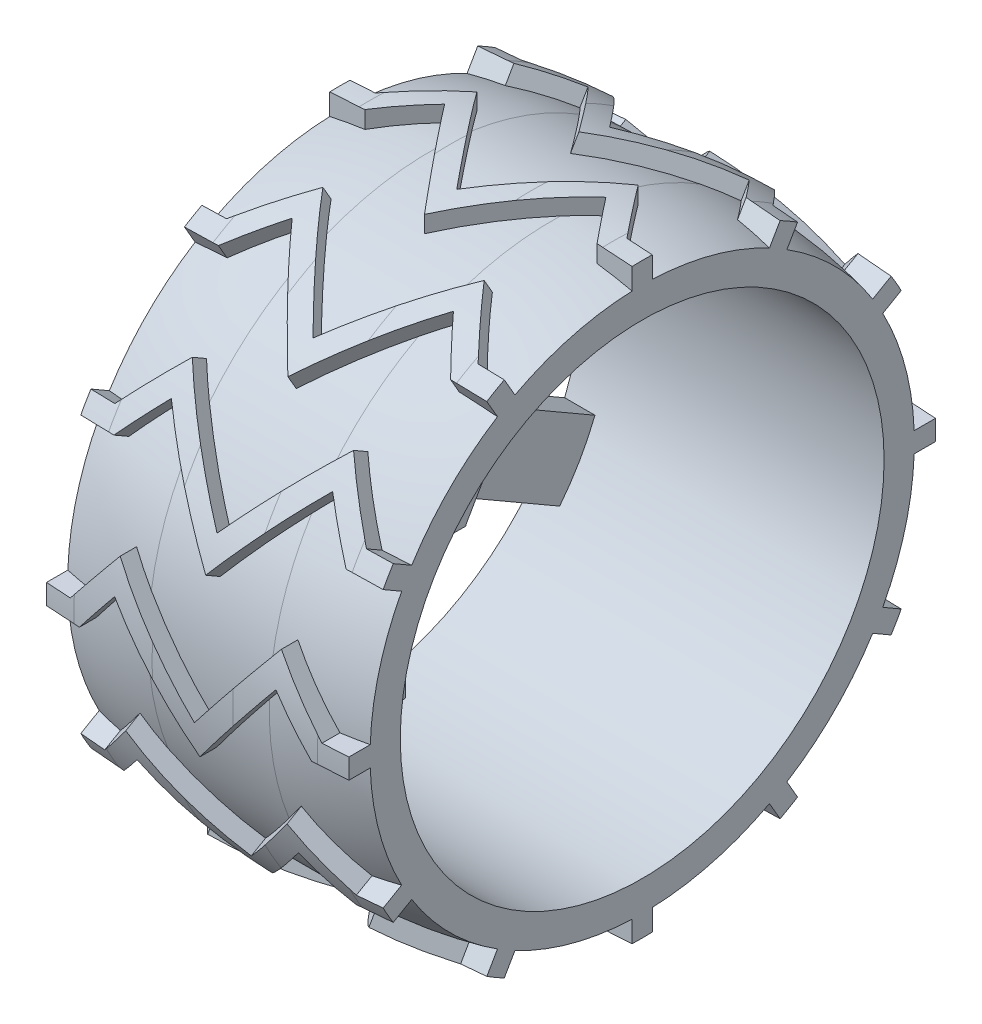
SolidWorks part; units mm, degrees
material "ABS"
ref_plane "Přední rovina" through (0, 0, 0) normal (0, 0, 1) x (1, 0, 0)
ref_plane "Horní rovina" through (0, 0, 0) normal (0, 1, 0) x (1, 0, 0)
ref_plane "Pravá rovina" through (0, 0, 0) normal (1, 0, 0) x (0, 0, -1)
sketch "Skica1" plane through (0, 0, 0) normal (0, 0, 1) x (1, 0, 0)
  line L0 (0, 0) -> (-19.9482, 0) construction
  line L1 (0, 0) -> (0, 24) construction
  line L2 (15, 24) -> (-15, 24)
  line L3 (-15, 24) -> (-15, 27)
  line L4 (0, 24) -> (0, 28) construction
  line L5 (6, 28) -> (-6, 28)
  line L6 (15, 24) -> (15, 27)
  arc A0 (-15, 27) -> (-6, 28) centre (-6, -13) cw
  arc A1 (15, 27) -> (6, 28) centre (6, -13) ccw
  dimension "D1" = 56
  dimension "D2" = 15
  dimension "D3" = 3
  dimension "D4" = 4
  dimension "D5" = 6
revolve "Rotovat1" add sketch "Skica1" angle 360 about L0 other way angle 360
ref_plane "Rovina1" through (0, 30, 0) normal (0, 1, 0) x (1, 0, 0)
sketch "Skica3" plane through (0, 30, 0) normal (0, 1, 0) x (1, 0, 0)
  line L0 (-15, 0) -> (-12, 0)
  line L1 (-15, 27) -> (-15, -27) construction
  line L2 (-12, 0) -> (-8, 5)
  line L3 (-8, 5) -> (-4, 0)
  line L4 (0, 0) -> (-10.2838, 0) construction
  line L5 (0, 0) -> (0, -5) construction
  line L6 (-8, 5) -> (-8, 0) construction
  line L7 (-4, 0) -> (0, -5)
  line L8 (4, 0) -> (0, -5)
  line L9 (8, 5) -> (4, 0)
  line L10 (12, 0) -> (8, 5)
  line L11 (15, 0) -> (12, 0)
  dimension "D1" = 5
  dimension "D2" = 3
extrude "Vysunout tenkostěnný1" add sketch "Skica3" against normal blind 10 thin thin type mid plane wall 2
pattern_circular "Kruhové pole1" count 12 over 360 about axis through (0, 0, 0) along (1, 0, 0) of "Vysunout tenkostěnný1"
sketch "Skica4" plane through (0, 0, 0) normal (1, 0, 0) x (0, 0, -1)
  circle A0 centre (0, 0) radius 24
  circle A1 centre (0, 0) radius 27
  circle A2 centre (0, 0) radius 24 construction
  dimension "D1" = 3
extrude "Odebrat vysunutím2" cut sketch "Skica4" against normal mid plane 30 contours A0 region at (0, 0, 0)
sketch "Skica5" plane through (0, 0, 0) normal (1, 0, 0) x (0, 0, -1)
  circle A0 centre (0, 0) radius 30
  circle A1 centre (0, 0) radius 24 construction
  circle A2 centre (0, 0) radius 40
  dimension "D1" = 6
  dimension "D2" = 10
extrude "Odebrat vysunutím3" cut sketch "Skica5" against normal mid plane 30
sketch "Skica6" plane through (0, 0, 0) normal (0, 0, 1) x (1, 0, 0)
  line L0 (-15, 26.9815) -> (-15, 29.9833) construction
  line L1 (-2, 28.618) -> (-4, 28.618) construction
  line L2 (-2, 28.618) -> (4, 28.618) construction
  line L3 (-2, 29.618) -> (4, 29.618)
  line L4 (-2, 29.618) -> (-4, 29.618)
  line L5 (-15, 29.113) -> (-18.0891, 33.8325)
  line L6 (-18.0891, 33.8325) -> (1.0133, 32.6178)
  line L7 (1.0133, 32.6178) -> (17.1086, 33.5822)
  line L8 (17.1086, 33.5822) -> (15, 29.113)
  line L9 (0, 0) -> (-14.4667, 0) construction
  line L10 (15, 26.9815) -> (15, 29.9833) construction
  arc A4 (-12, 28.2983) -> (-14, 28.118) centre (-4, -71.632) ccw construction
  arc A5 (-4, 28.618) -> (-12, 28.2983) centre (-4, -71.632) ccw construction
  arc A6 (14, 28.118) -> (12, 28.2983) centre (4, -71.632) ccw construction
  arc A7 (12, 28.2983) -> (4, 28.618) centre (4, -71.632) ccw construction
  arc A8 (15, 29.113) -> (12.0798, 29.2951) centre (7.2394, -71.8391) ccw
  arc A9 (12.0798, 29.2951) -> (4, 29.618) centre (4, -71.632) ccw
  arc A10 (-4, 29.618) -> (-12.0798, 29.2951) centre (-4, -71.632) ccw
  arc A11 (-12.0798, 29.2951) -> (-15, 29.113) centre (-7.2394, -71.8391) ccw
revolve "Odebrat rotací1" cut sketch "Skica6" angle 360 about L9 region at (-0.4869, 31.3717, 0)
sketch "Skica7" plane through (0, 0, 0) normal (0, 0, 1) x (1, 0, 0)
  line L0 (-6, 0) -> (-27.797, 0) construction
  line L1 (-15, 24) -> (-15, 13)
  line L2 (-15, 12.6247) -> (-15, 1) construction
  line L4 (-15, 13) -> (-15, 0)
  line L5 (-15, 0) -> (-6, 0)
  line L6 (-6, 0) -> (-6, 5.9654)
  line L7 (-6, 5.9654) -> (-12, 11)
  line L8 (-12, 11) -> (-12, 24)
  line L9 (-12, 24) -> (-15, 24)
  line L10 (-15, -1) -> (-15, -12.6247) construction
  dimension "D1" = 3
  dimension "D2" = 13
  dimension "D3" = 9
  dimension "D4" = 130
  dimension "D5" = 11
extrude "Přidat vysunutím1" add sketch "Skica7" along normal mid plane 7
pattern_circular "Kruhové pole2" count 6 over 360 of "Přidat vysunutím1"
sketch "Skica9" plane through (-15, 0, 0) normal (-1, 0, 0) x (0, 0, 1)
  circle A0 centre (0, 0) radius 3.25
  dimension "D1" = 6.5
extrude "Odebrat vysunutím4" cut sketch "Skica9" against normal blind 4
sketch "Skica10" plane through (-11, 0, 0) normal (-1, 0, 0) x (0, 0, 1)
  circle A0 centre (0, 0) radius 1.4
  dimension "D1" = 2.8
extrude "Odebrat vysunutím5" cut sketch "Skica10" against normal blind 12
sketch "Skica13" plane through (-6, 0, 0) normal (1, 0, 0) x (0, 0, -1)
  circle A0 centre (0, 0) radius 3.25
  dimension "D1" = 6.5
extrude "Odebrat vysunutím7" cut sketch "Skica13" against normal blind 2
scale "Scale1" scale about centroid uniform scaling yes scale factor 10
